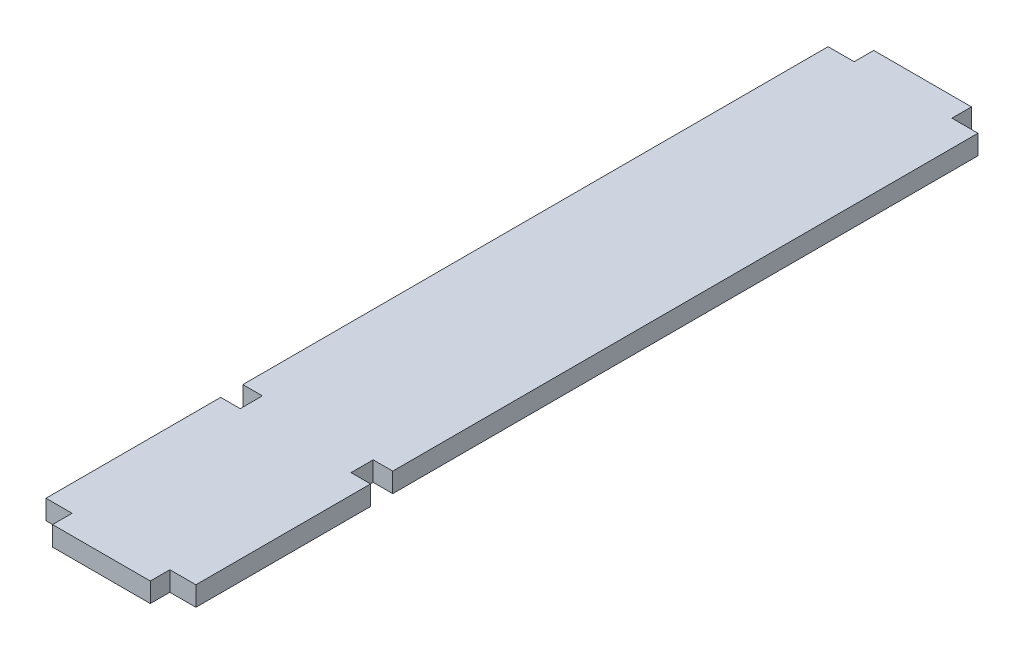
SolidWorks part; units mm, degrees
material "AISI 304"
ref_plane "Front Plane" through (0, 0, 0) normal (0, 0, 1) x (1, 0, 0)
ref_plane "Top Plane" through (0, 0, 0) normal (0, 1, 0) x (1, 0, 0)
ref_plane "Right Plane" through (0, 0, 0) normal (1, 0, 0) x (0, 0, -1)
sketch "Sketch1" plane through (0, 0, 0) normal (0, 1, 0) x (1, 0, 0)
  line L0 (3.75, 30) -> (5.75, 30)
  line L1 (-5.75, -30) -> (-3.75, -30)
  line L2 (-5.75, -30) -> (-5.75, -16.6)
  line L3 (-5.75, 30) -> (-3.75, 30)
  line L4 (5.75, -30) -> (5.75, -16.6)
  line L5 (-5.75, -30) -> (5.75, 30) construction
  line L6 (-5.75, 30) -> (5.75, -30) construction
  line L8 (3.75, 30) -> (3.75, 31.5)
  line L9 (3.75, 31.5) -> (-3.75, 31.5)
  line L10 (-3.75, 30) -> (-3.75, 31.5)
  line L12 (-3.75, -30) -> (-3.75, -31.5)
  line L13 (-3.75, -31.5) -> (3.75, -31.5)
  line L14 (3.75, -30) -> (3.75, -31.5)
  line L15 (3.75, -30) -> (5.75, -30)
  line L16 (-5.75, -14.9) -> (-5.75, 30)
  line L17 (-5.75, -14.9) -> (-4.25, -14.9)
  line L19 (-5.75, -16.6) -> (-4.25, -16.6)
  line L20 (-4.25, -14.9) -> (-4.25, -16.6)
  line L21 (5.75, -14.9) -> (5.75, 30)
  line L22 (5.75, -16.6) -> (4.25, -16.6)
  line L24 (5.75, -14.9) -> (4.25, -14.9)
  line L25 (4.25, -16.6) -> (4.25, -14.9)
  point P0 (0, 0)
  point P22 (0, -31.5)
  dimension "D1" = 7.5
  dimension "D2" = 2
  dimension "D3" = 2
  dimension "D4" = 1.5
  dimension "D5" = 2
  dimension "D6" = 2
  dimension "D7" = 1.5
  dimension "D8" = 60
  dimension "D9" = 8.5
  dimension "D10" = 4.25
extrude "Boss-Extrude1" add sketch "Sketch1" along normal blind 1.5
